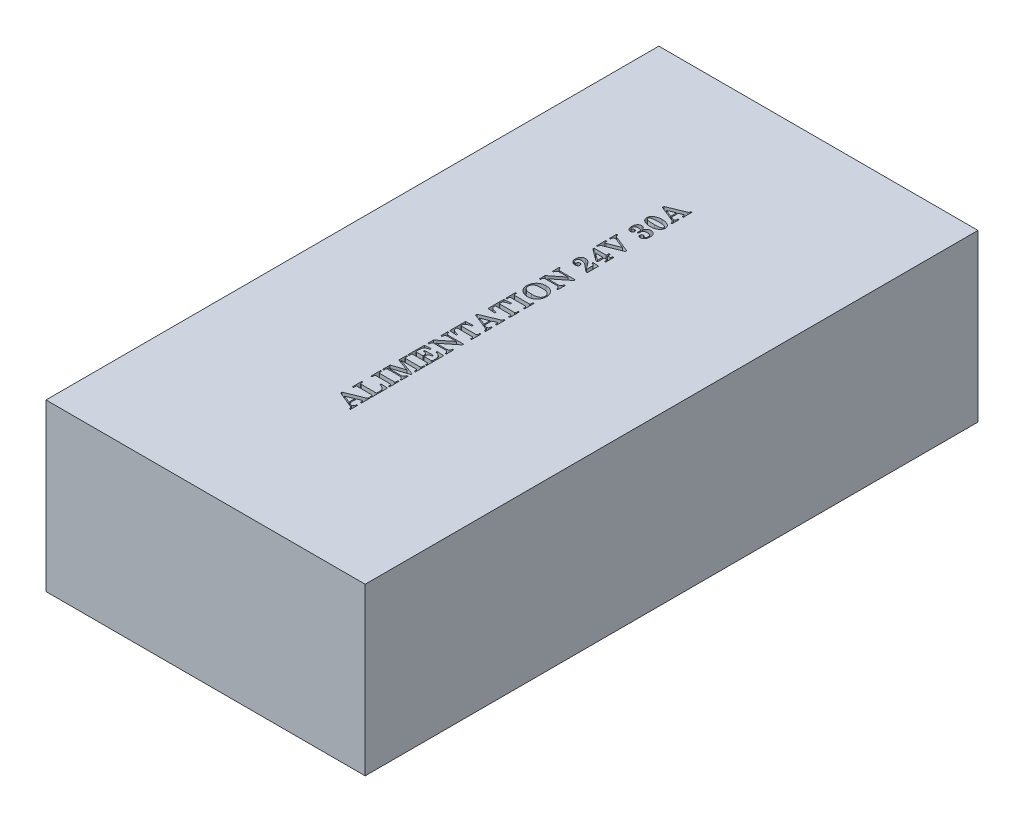
SolidWorks part; units mm, degrees
ref_plane "Plan de face" through (0, 0, 0) normal (0, 0, 1) x (1, 0, 0)
ref_plane "Plan de dessus" through (0, 0, 0) normal (0, 1, 0) x (1, 0, 0)
ref_plane "Plan de droite" through (0, 0, 0) normal (1, 0, 0) x (0, 0, -1)
sketch "Esquisse1" plane through (0, 0, 0) normal (0, 0, 1) x (1, 0, 0)
  line L1 (62.5, -32.5) -> (-62.5, -32.5)
  line L2 (62.5, -32.5) -> (62.5, 32.5)
  line L3 (62.5, 32.5) -> (-62.5, 32.5)
  line L4 (-62.5, -32.5) -> (-62.5, 32.5)
  line L5 (62.5, -32.5) -> (-62.5, 32.5) construction
  line L6 (62.5, 32.5) -> (-62.5, -32.5) construction
  point P0 (0, 0)
  dimension "D1" = 65
  dimension "D2" = 125
extrude "Boss.-Extru.1" add sketch "Esquisse1" against normal blind 240
sketch "Esquisse2" plane through (0, 32.5, 0) normal (0, 1, 0) x (1, 0, 0)
  line L0 (0.3498, 0) -> (0.3498, 240) construction
  line L1 (62.5, 0) -> (-62.5, 0) construction
  line L2 (62.5, 240) -> (-62.5, 240) construction
  text T0 "<b>ALIMENTATION 24V 30A</b>" font "Century Schoolbook" height in points 28
  point P5 (6.7938, 240)
extrude "Enlèv. mat.-Extru.1" cut sketch "Esquisse2" against normal blind 10
